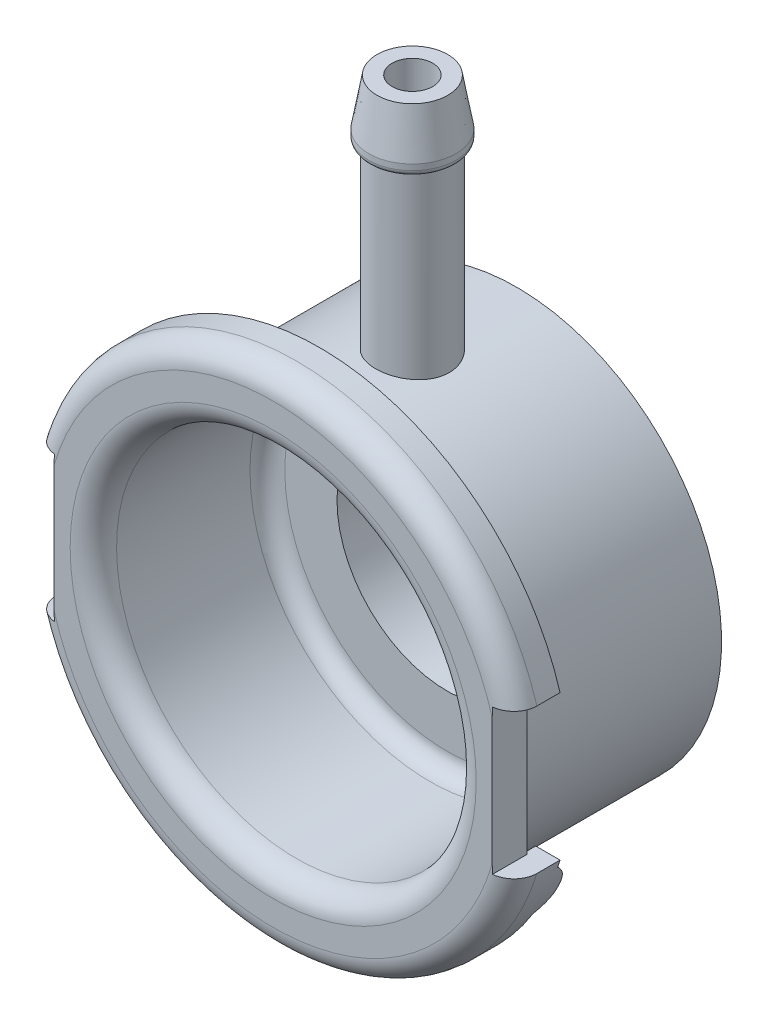
SolidWorks part; units mm, degrees
material "Custom Plastic"
ref_plane "X-Y Datum" through (0, 0, 0) normal (0, 0, 1) x (1, 0, 0)
ref_plane "X-Z Datum" through (0, 0, 0) normal (0, 1, 0) x (1, 0, 0)
ref_plane "Y-Z Datum" through (0, 0, 0) normal (1, 0, 0) x (0, 0, -1)
sketch "Sketch1" plane through (0, 0, 0) normal (0, 0, 1) x (1, 0, 0)
  circle A0 centre (0, 0) radius 17.65
  circle A1 centre (0, 0) radius 15.5
  dimension "D1" = 35.3
  dimension "D2" = 31
extrude "Boss-Extrude1" add sketch "Sketch1" along normal blind 18
sketch "Sketch2" plane through (0, 0, 18) normal (0, 0, 1) x (1, 0, 0)
  circle A0 centre (0, 0) radius 15.5
  circle A1 centre (0, 0) radius 21.65
  circle A2 centre (0, 0) radius 15.5 construction
  dimension "D1" = 43.3
extrude "Boss-Extrude2" add sketch "Sketch2" against normal blind 3
sketch "Sketch3" plane through (0, 0, 18) normal (0, 0, 1) x (1, 0, 0)
  line L0 (0, 15.5) -> (0, -15.5) construction
  line L1 (18.88, -6.25) -> (23.88, -6.25)
  line L2 (18.88, -6.25) -> (18.88, 6.25)
  line L3 (18.88, 6.25) -> (23.88, 6.25)
  line L4 (23.88, -6.25) -> (23.88, 6.25)
  line L5 (-18.88, -6.25) -> (-23.88, -6.25)
  line L6 (-23.88, -6.25) -> (-23.88, 6.25)
  line L7 (-18.88, 6.25) -> (-23.88, 6.25)
  line L8 (-18.88, -6.25) -> (-18.88, 6.25)
  circle A0 centre (0, 0) radius 15.5 construction
  point P4 (18.88, 0)
  dimension "D1" = 18.88
  dimension "D2" = 12.5
  dimension "D3" = 5
extrude "Cut-Extrude1" cut sketch "Sketch3" against normal through all
sketch "Sketch4" plane through (0, 0, 15) normal (0, 0, -1) x (-1, 0, 0)
  line L0 (-20.7282, -6.25) -> (-18.6295, -6.25)
  line L1 (-18.88, -6.25) -> (-20.7282, -6.25) construction
  line L2 (-20.7282, 6.25) -> (-18.6295, 6.25)
  line L3 (20.7282, -6.25) -> (18.6295, -6.25)
  line L4 (20.7282, 6.25) -> (18.6295, 6.25)
  arc A0 (-20.7282, -6.25) -> (20.7282, -6.25) centre (0, 0) ccw
  arc A1 (-18.6295, -6.25) -> (18.6295, -6.25) centre (0, 0) ccw
  arc A2 (-20.7282, -6.25) -> (20.7282, -6.25) centre (0, 0) ccw construction
  arc A3 (20.7282, 6.25) -> (-20.7282, 6.25) centre (0, 0) ccw
  arc A4 (18.6295, 6.25) -> (-18.6295, 6.25) centre (0, 0) ccw
  dimension "D1" = 2
extrude "Boss-Extrude3" add sketch "Sketch4" along normal blind 1
sketch "Sketch5" plane through (0, 0, 14) normal (0, 0, -1) x (-1, 0, 0)
  line L0 (-18.6295, -6.25) -> (-20.5257, -6.8861)
  line L1 (-16.699, -10.357) -> (-18.3986, -11.4111)
  arc A0 (-20.7282, -6.25) -> (20.7282, -6.25) centre (0, 0) ccw construction
  arc A1 (-18.3986, -11.4111) -> (-20.5257, -6.8861) centre (0, 0) cw
  arc A2 (-16.699, -10.357) -> (-18.6295, -6.25) centre (0, 0) cw
  arc A3 (-18.6295, -6.25) -> (18.6295, -6.25) centre (0, 0) ccw construction
  dimension "D1" = 5
extrude "Boss-Extrude4" add sketch "Sketch5" along normal blind 1
sketch3d "3DSketch1"
  line L0 (0, 0, 0) -> (0, 0, 18)
pattern_circular "CirPattern1" count 2 over 360 about axis through (0, 0, 0) along (0, 0, 1) of "Boss-Extrude4"
fillet "Fillet1" radius 3 4 edges at (-17.5488, 10.8841, 13) (-19.5776, 6.5681, 13) (17.5488, -10.8841, 13) (19.5776, -6.5681, 13)
fillet "Fillet2" radius 2 3 edges at (0, 21.65, 18) (15.5, 0, 18) (0, -21.65, 18)
sketch "Sketch6" plane through (0, 0, 0) normal (0, 1, 0) x (1, 0, 0)
  line L0 (-18.88, -18) -> (18.88, -18) construction
  circle A0 centre (0, -6) radius 3.175
  circle A1 centre (0, -6) radius 1.75
  dimension "D2" = 6.35
  dimension "D3" = 3.5
  dimension "D1" = 12
extrude "Cut-Extrude2" cut sketch "Sketch6" along normal through all contours A1 region at (0, 0, 6)
extrude "Boss-Extrude5" add sketch "Sketch6<4>" against normal up to next from offset 38
sketch "Sketch6<4>" plane through (0, 0, 0) normal (0, 1, 0) x (1, 0, 0) same geometry as "Sketch6"
sketch "Sketch7" plane through (0, 38, 0) normal (0, 1, 0) x (1, 0, 0)
  circle A0 centre (0, -6) radius 3.755
  circle A1 centre (0, -6) radius 1.75
  circle A2 centre (0, -6) radius 1.75 construction
  dimension "D1" = 7.51
extrude "Boss-Extrude6" add sketch "Sketch7" against normal blind 5
chamfer "Chamfer1" distance 4 angle 10 1 edges at (0, 38, 9.755) first distance on face at (0, 33, 9.755)
sketch "Sketch8" plane through (0, 0, 0) normal (0, 0, -1) x (-1, 0, 0)
  circle A0 centre (0, 0) radius 17.65
  circle A1 centre (0, 0) radius 9.5
  circle A2 centre (0, 0) radius 17.65 construction
  dimension "D1" = 19
extrude "Boss-Extrude7" add sketch "Sketch8" along normal blind 3 and the other way blind 3
fillet "Fillet4" radius 1.5 1 edges at (-15.5, 0, 3)
fillet "Fillet5" radius 0.5 1 edges at (0, 33, 9.755)
